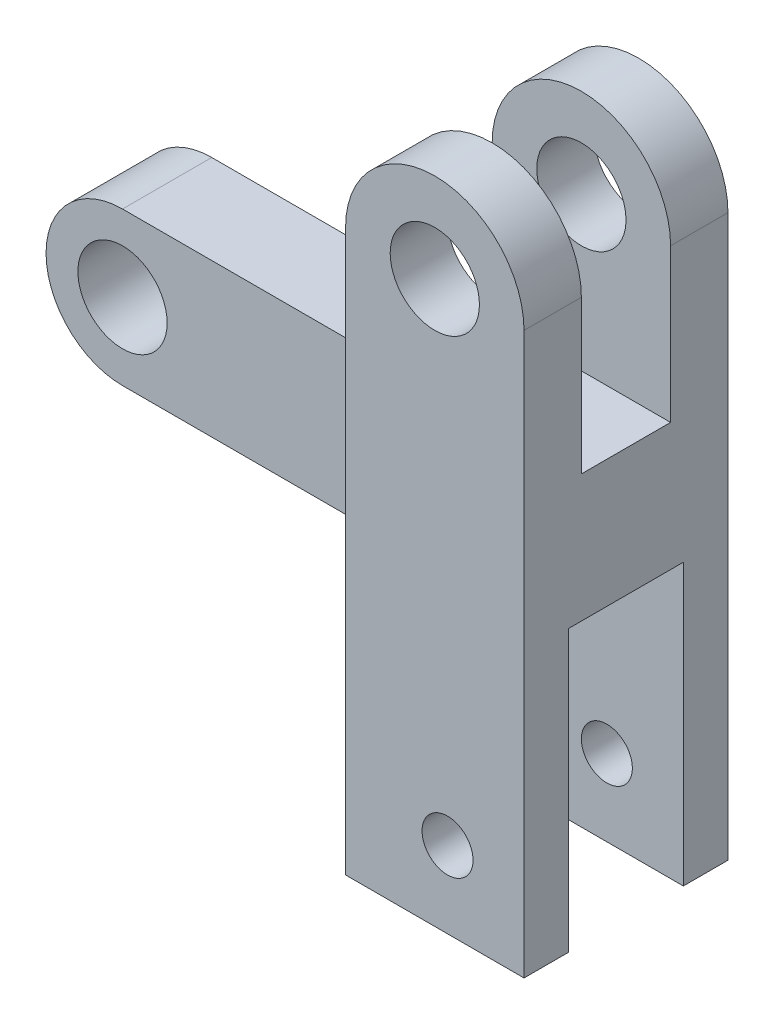
SolidWorks part; units mm, degrees
ref_plane "前视基准面" through (0, 0, 0) normal (0, 0, 1) x (1, 0, 0)
ref_plane "上视基准面" through (0, 0, 0) normal (0, 1, 0) x (1, 0, 0)
ref_plane "右视基准面" through (0, 0, 0) normal (1, 0, 0) x (0, 0, -1)
other "Configuration Table"
sketch "草图1" plane through (0, 0, 0) normal (0, 1, 0) x (1, 0, 0)
  line L1 (0, 3.5) -> (7, 3.5)
  line L2 (0, -3.5) -> (7, -3.5)
  line L3 (0, 3.5) -> (7, 3.5) construction
  line L4 (7, 3.5) -> (7, -3.5)
  line L5 (0, 3.5) -> (0, -3.5)
  dimension "D1" = 7
  dimension "D4" = 90
  dimension "D5" = 7
extrude "凸台-拉伸1" add sketch "草图1" along normal blind 2.4
sketch "草图10" plane through (0, 0, -3.5) normal (0, 0, -1) x (-1, 0, 0)
  line L3 (-7, 2.4) -> (0, 2.4) construction
  line L6 (-7, 2.4) -> (0, 2.4)
  line L7 (0, 2.4) -> (0, 10)
  line L9 (-7, 10) -> (-7, 2.4)
  line L10 (0, 2.4) -> (0, 0) construction
  arc A1 (0, 10) -> (-7, 10) centre (-3.5, 10) ccw
  line M3 (0, 2.4) -> (-7, 2.4)
  dimension "D8" = 3.5
  dimension "D9" = 10
extrude "凸台-拉伸6" add sketch "草图10" against normal blind 1.75 contours L7 A1 L9 M3 region at (3.5, 7.6039, -3.5)
extrude "凸台-拉伸8" add sketch "草图10<2>" along normal blind 1.75 from offset 7 contours L7 A1 L9 M3 region at (3.5, 7.6039, -3.5) offset against normal yes
sketch "草图10<2>" plane through (0, 0, -3.5) normal (0, 0, -1) x (-1, 0, 0) same geometry as "草图10"
sketch "草图11" plane through (0, 0, -3.5) normal (0, 0, -1) x (-1, 0, 0)
  circle A2 centre (-3.5, 10) radius 1.75
  dimension "D3" = 3.5
extrude "切除-拉伸1" cut sketch "草图11" against normal through all
sketch "草图17" plane through (0, 0, 0) normal (0, -1, 0) x (1, 0, 0)
  line L6 (0, 3.5) -> (0, -3.5)
  line L7 (0, -3.5) -> (7, -3.5)
  line L8 (7, -3.5) -> (7, 3.5)
  line L9 (7, 3.5) -> (0, 3.5)
  line L12 (0, 3.5) -> (0, -3.5)
  line L13 (0, -3.5) -> (7, -3.5)
  line L14 (7, -3.5) -> (7, 3.5)
  line L15 (7, 3.5) -> (0, 3.5)
  dimension "D1" = 0
extrude "凸台-拉伸10" add sketch "草图17" along normal blind 12
sketch "草图15" plane through (0, 0, 0) normal (0, 0, 1) x (1, 0, 0)
  line L2 (7, 4) -> (7, -2)
  line L10 (7, 10) -> (7, -12) construction
  line L14 (-11, 4) -> (7, 4)
  line L15 (7, 10) -> (7, -12) construction
  line L17 (7, 2.4) -> (7.3779, 2.4)
  line L18 (0, 2.4) -> (7, 2.4) construction
  line L19 (-11, -2) -> (7, -2)
  line L20 (7, -12) -> (0, -12) construction
  arc A0 (-11, -2) -> (-11, 4) centre (-11, 1) cw
  circle A1 centre (-11, 1) radius 1.75
  dimension "D3" = 3.5
  dimension "D1" = 3
  dimension "D2" = 10
  dimension "D4" = 18
extrude "凸台-拉伸9" add sketch "草图15" along normal mid plane 3.5 contours A0 L19 L2 L14 A1 region at (-2.5212, 1, 0)
sketch "草图12" plane through (0, 4, 3.5) normal (0, 0, -1) x (1, 0, 0)
  line L0 (0, 16) -> (7, 16) construction
  line L2 (7, -6) -> (7, 16) construction
  circle A0 centre (4, 13) radius 1
  dimension "D2" = 2
  dimension "D1" = 3
  dimension "D3" = 3
extrude "切除-拉伸2" cut sketch "草图12" along normal through all
sketch "草图18" plane through (7.4, -12, 0) normal (0, 1, 0) x (1, 0, 0)
  line L0 (-0.4, 1.75) -> (-0.4, 3.5) construction
  line L11 (-7.4, -2.25) -> (-0.4, -2.25)
  line L12 (-7.4, -2.25) -> (-7.4, 2.25)
  line L13 (-7.4, 2.25) -> (-0.4, 2.25)
  line L14 (-0.4, -2.25) -> (-0.4, 2.25)
  point P4 (-7.4, 0)
  dimension "D1" = 4.5
  dimension "D2" = 7
extrude "切除-拉伸4" cut sketch "草图18" along normal blind 11
sketch "草图19" plane through (0, 0, 3.5) normal (0, 0, 1) x (1, 0, 0)
  line L4 (0, 10) -> (0, -12)
  line L5 (0, -12) -> (7, -12)
  line L6 (7, -12) -> (7, 10)
  line L8 (0, 10) -> (0, -12)
  line L9 (0, -12) -> (7, -12)
  line L10 (7, -12) -> (7, 10)
  circle A0 centre (4, -9) radius 1 construction
  circle A1 centre (4, -9) radius 1
  circle A2 centre (3.5, 10) radius 1.75 construction
  arc A3 (7, 10) -> (0, 10) centre (3.5, 10) ccw
  arc A4 (7, 10) -> (0, 10) centre (3.5, 10) ccw
  circle A5 centre (3.5, 10) radius 1.75
  dimension "D1" = 0
extrude "凸台-拉伸11" add sketch "草图19" along normal blind 0.5
sketch "草图20" plane through (0, 0, -3.5) normal (0, 0, -1) x (-1, 0, 0)
  line L4 (-7, 10) -> (-7, -12)
  line L5 (-7, -12) -> (0, -12)
  line L6 (0, -12) -> (0, 10)
  line L8 (-7, 10) -> (-7, -12)
  line L9 (-7, -12) -> (0, -12)
  line L10 (0, -12) -> (0, 10)
  circle A0 centre (-4, -9) radius 1 construction
  circle A1 centre (-4, -9) radius 1
  circle A2 centre (-3.5, 10) radius 1.75 construction
  arc A3 (0, 10) -> (-7, 10) centre (-3.5, 10) ccw
  arc A4 (0, 10) -> (-7, 10) centre (-3.5, 10) ccw
  circle A5 centre (-3.5, 10) radius 1.75
  dimension "D1" = 0
extrude "凸台-拉伸12" add sketch "草图20" along normal blind 0.5
